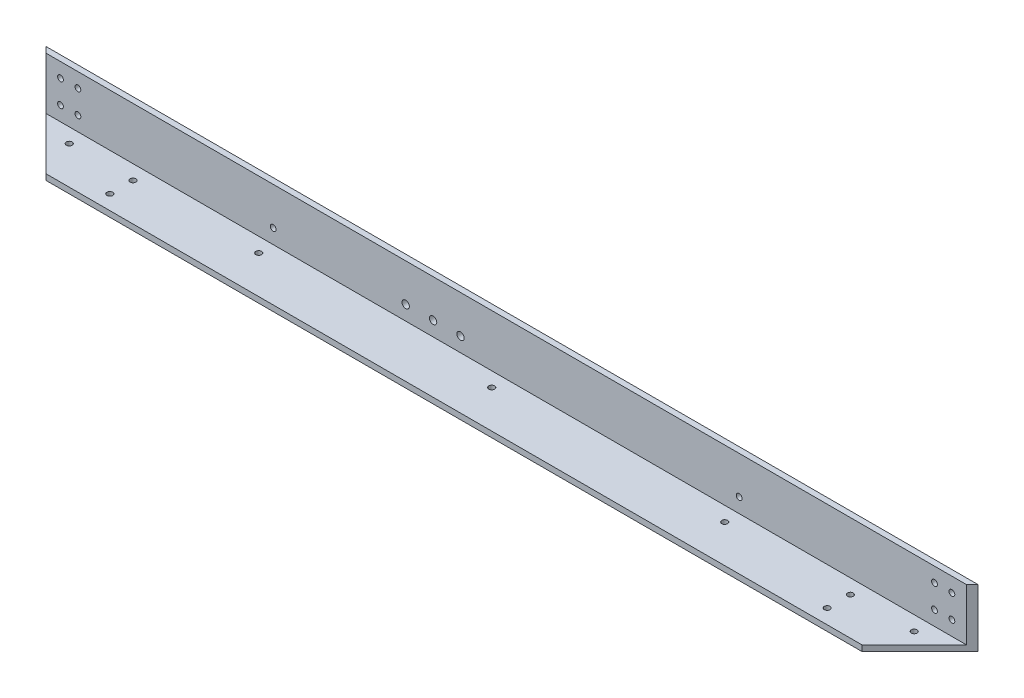
SolidWorks part; units mm, degrees
ref_plane "Front Plane" through (0, 0, 0) normal (0, 0, 1) x (1, 0, 0)
ref_plane "Top Plane" through (0, 0, 0) normal (0, 1, 0) x (1, 0, 0)
ref_plane "Right Plane" through (0, 0, 0) normal (1, 0, 0) x (0, 0, -1)
sketch "Sketch1" plane through (0, 0, 0) normal (1, 0, 0) x (0, 0, -1)
  line L0 (0, 0) -> (-31.75, 0)
  line L1 (-31.75, 0) -> (-31.75, 3.175)
  line L2 (-31.75, 3.175) -> (-3.175, 3.175)
  line L3 (-3.175, 3.175) -> (-3.175, 31.75)
  line L4 (-3.175, 31.75) -> (0, 31.75)
  line L5 (0, 31.75) -> (0, 0)
  dimension "LHeight" = 31.75
  dimension "LWidth" = 31.75
  dimension "LMaterialThickness" = 3.175
  dimension "D1" = 28.575
  dimension "D2" = 28.575
  dimension "D3" = 3.175
extrude "Boss-Extrude1" add sketch "Sketch1" along normal blind 510
chamfer "Chamfer6" distance 31.75 angle 45 1 edges at (510, 1.5875, 31.75)
chamfer "Chamfer7" distance 31.75 angle 45 1 edges at (0, 1.5875, 31.75)
sketch "TopHoles-Sketch3" plane through (0, 3.175, 0) normal (0, 1, 0) x (1, 0, 0)
  line L1 (478.25, -31.75) -> (31.75, -31.75) construction
  line L2 (510, 0) -> (0, 0) construction
  circle A5 centre (58.7375, -23.8125) radius 1.5875
  circle A6 centre (451.2625, -23.8125) radius 1.5875
  circle A9 centre (451.2625, -11.1125) radius 1.5875
  circle A10 centre (58.7375, -11.1125) radius 1.5875
  circle A11 centre (486.1875, -11.1125) radius 1.5875
  circle A12 centre (23.8125, -11.1125) radius 1.5875
  circle A13 centre (127.5, -11.1125) radius 1.5875
  circle A14 centre (255, -11.1125) radius 1.5875
  circle A15 centre (382.5, -11.1125) radius 1.5875
  dimension "D9" = 3.175
  dimension "D12" = 7.9375
  dimension "D2" = 11.1125
  dimension "D3" = 23.8125
  dimension "D6" = 23.8125
  dimension "D4" = 12.7
  dimension "D5" = 34.925
  dimension "D7" = 34.925
  dimension "D8" = 127.5
  dimension "D10" = 127.5
  dimension "D11" = 127.5
  dimension "D13" = 68.7625
extrude "TopHoles-Cut-Extrude2" cut sketch "TopHoles-Sketch3" against normal through all
sketch "BackHoles-Sketch4" plane through (0, 0, 3.175) normal (0, 0, 1) x (1, 0, 0)
  line L0 (0, 0) -> (0, 31.75) construction
  line L1 (510, 0) -> (510, 31.75) construction
  line L2 (478.25, 0) -> (31.75, 0) construction
  line L7 (510, 0) -> (0, 0) construction
  line L8 (510, 31.75) -> (0, 31.75) construction
  circle A1 centre (11.1125, 23.8125) radius 1.5875
  circle A3 centre (489.3625, 23.8125) radius 1.5875
  circle A4 centre (20.6375, 23.8125) radius 1.5875
  circle A5 centre (498.8875, 23.8125) radius 1.5875
  circle A6 centre (11.1125, 11.1125) radius 1.5875
  circle A7 centre (20.6375, 11.1125) radius 1.5875
  circle A8 centre (489.3625, 11.1125) radius 1.5875
  circle A9 centre (498.8875, 11.1125) radius 1.5875
  circle A10 centre (200, 11.1125) radius 2
  circle A11 centre (215, 11.1125) radius 2
  circle A12 centre (230, 11.1125) radius 2
  circle A13 centre (127.5, 11.1125) radius 1.5875
  circle A14 centre (382.5, 11.1125) radius 1.5875
  dimension "D2" = 3.175
  dimension "D11" = 4
  dimension "D7" = 11.1125
  dimension "D4" = 7.9375
  dimension "D1" = 11.1125
  dimension "D6" = 20.6375
  dimension "D3" = 11.1125
  dimension "D5" = 20.6375
  dimension "D8" = 215
  dimension "D9" = 15
  dimension "D10" = 15
  dimension "D12" = 11.1125
  dimension "D13" = 127.5
  dimension "D14" = 127.5
extrude "BackHoles-Cut-Extrude3" cut sketch "BackHoles-Sketch4" against normal through all
equation "\"TopRailWidth\"= 1.25in"
equation "\"TopRailHeight\"= 1.25in"
equation "\"RailThickness\"= .125in'Spec"
equation "\"SideRailHoleY1FromEdge\"= \"HoleOffsetFromEdge\""
equation "\"SideRailHoleX1FromSide\"= \"HoleOffsetFromSide\""
equation "\"VSWidth\"= 1.25in'Spec"
equation "\"HoleOffsetFromEdge\"= \"RailThickness\" * 2.5"
equation "\"HoleOffsetFromSide\"= \"RailThickness\" * 3.5"
equation "\"TopCBWidth\"= \"TopRailWidth\" - \"RailThickness\"'Equals 28.575"
equation "\"SideRailHoleX2FromSide\"= \"VSWidth\" - \"HoleOffsetFromEdge\" - \"RailThickness\"'Equals 20.6375"
equation "\"FasteningHoleDiameter\"= .125in"
equation "\"SideRailHoleY2FromSide\"= \"HoleOffsetFromSide\""
equation "\"D2@BackHoles-Sketch4\"=\"FasteningHoleDiameter\""
equation "\"LWidth@Sketch1\"=\"TopRailWidth\""
equation "\"LHeight@Sketch1\"=\"TopRailHeight\""
equation "\"LMaterialThickness@Sketch1\"=\"RailThickness\""
equation "\"D1@Boss-Extrude1\"= \"FrontBackRailLength\""
equation "\"FrontBackRailLength\"= 510mm"
equation "\"D7@BackHoles-Sketch4\"=\"SideRailHoleY2FromSide\""
equation "\"D4@BackHoles-Sketch4\"=\"SideRailHoleY1FromEdge\""
equation "\"D1@Chamfer6\"=\"TopRailWidth\""
equation "\"D1@Chamfer7\"=\"TopRailWidth\""
equation "\"D6@TopHoles-Sketch3\"=\"TopHoleX1FromEdge\" + \"RailThickness\""
equation "\"D1@BackHoles-Sketch4\"=\"SideRailHoleX1FromSide\""
equation "\"D6@BackHoles-Sketch4\"=\"SideRailHoleX2FromSide\""
equation "\"D5@BackHoles-Sketch4\"=\"SideRailHoleX2FromSide\""
equation "\"D3@BackHoles-Sketch4\" = \"SideRailHoleX1FromSide\""
equation "\"D8@BackHoles-Sketch4\"=\"FrontBackRailLength\"/2 - 40mm"
equation "\"TopHoleX1FromEdge\"= \"TopCBWidth\" - \"HoleOffsetFromEdge\"'Equals 20.6375"
equation "\"TopHoleX2FromX1\"= \"TopCBLength\" - \"TopHoleX1FromEdge\" - \"HoleOffsetFromEdge\"'Equals 34.925"
equation "\"TopHoleY1FromSide\"= \"HoleOffsetFromSide\""
equation "\"TopHoleY2FromY1\"= \"TopCBWidth\" - \"TopHoleY1FromEdge\" - \"HoleOffsetFromEdge\"'Equals 12.7"
equation "\"D2@TopHoles-Sketch3\"=\"TopHoleY1FromSide\""
equation "\"D4@TopHoles-Sketch3\"=\"TopHoleY2FromY1\""
equation "\"D5@TopHoles-Sketch3\"=\"TopHoleX2FromX1\""
equation "\"D7@TopHoles-Sketch3\"=\"TopHoleX2FromX1\""
equation "\"TopCBLength\"= \"TopRailWidth\" * 2'Equals 63.5"
equation "\"TopHoleY1FromEdge\"= \"HoleOffsetFromEdge\""
equation "\"D3@TopHoles-Sketch3\"=\"TopHoleX1FromEdge\" + \"RailThickness\""
equation "\"FrontOrBackEnclosureOffsets\"= \"FrontBackRailLength\" / 4"
equation "\"D8@TopHoles-Sketch3\"=\"FrontOrBackEnclosureOffsets\""
equation "\"D11@TopHoles-Sketch3\"=\"FrontOrBackEnclosureOffsets\""
equation "\"D10@TopHoles-Sketch3\"=\"FrontOrBackEnclosureOffsets\""
equation "\"D13@BackHoles-Sketch4\"=\"FrontOrBackEnclosureOffsets\""
equation "\"D14@BackHoles-Sketch4\"=\"FrontOrBackEnclosureOffsets\""
